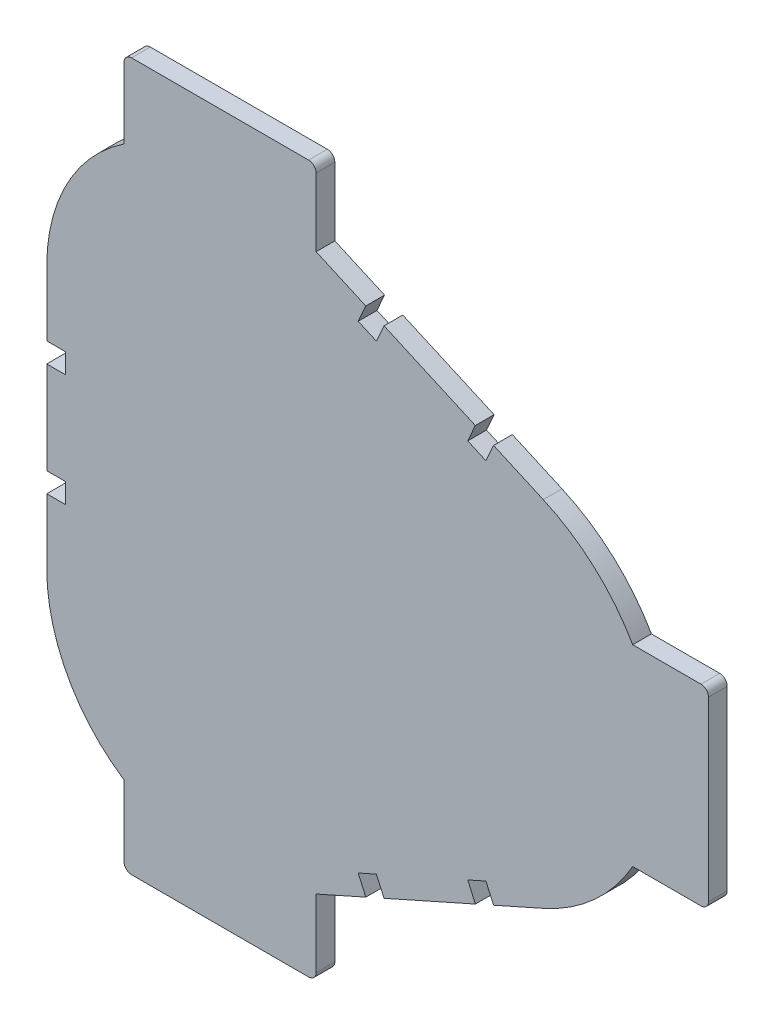
SolidWorks part; units mm, degrees
ref_plane "Front Plane" through (0, 0, 0) normal (0, 0, 1) x (1, 0, 0)
ref_plane "Top Plane" through (0, 0, 0) normal (0, 1, 0) x (1, 0, 0)
ref_plane "Right Plane" through (0, 0, 0) normal (1, 0, 0) x (0, 0, -1)
sketch "Sketch1" plane through (0, 0, -130.81) normal (0, 0, -1) x (-1, 0, 0)
  line L0 (70.5268, 62.4132) -> (70.5268, 49.4592) construction
  line L1 (70.5268, 49.4592) -> (76.8768, 49.4592) construction
  line L2 (76.8768, 49.4592) -> (76.8768, 62.4132) construction
  line L3 (76.8768, 62.4132) -> (70.5268, 62.4132) construction
  line L4 (70.5268, 24.3132) -> (70.5268, 11.3592) construction
  line L5 (70.5268, 11.3592) -> (76.8768, 11.3592) construction
  line L6 (76.8768, 11.3592) -> (76.8768, 24.3132) construction
  line L7 (76.8768, 24.3132) -> (70.5268, 24.3132) construction
  line L8 (76.8768, 52.558) -> (70.5268, 52.558) construction
  line L9 (70.5268, 52.558) -> (70.5268, 21.2144) construction
  line L10 (70.5268, 21.2144) -> (76.8768, 21.2144) construction
  line L11 (76.8768, 21.2144) -> (76.8768, 52.558) construction
  line L12 (-8.0545, -76.637) -> (-8.0545, -54.8958) construction
  line L13 (-9.5612, -52.5755) -> (-28.6575, -44.0718) construction
  line L14 (-28.6575, -44.0718) -> (-31.2406, -49.8726) construction
  line L15 (-31.2406, -49.8726) -> (-14.4045, -57.3699) construction
  line L16 (-14.4045, -57.3699) -> (-14.4045, -80.447) construction
  line L17 (-11.8645, -82.987) -> (48.143, -82.987) construction
  line L18 (50.683, -80.447) -> (50.683, -56.4617) construction
  line L19 (76.8768, -7.5638) -> (76.8768, 14.458) construction
  line L20 (76.8768, 14.458) -> (70.5268, 14.458) construction
  line L21 (70.5268, 14.458) -> (70.5268, -7.5638) construction
  line L22 (44.333, -54.3762) -> (44.333, -76.637) construction
  line L23 (44.333, -76.637) -> (-8.0545, -76.637) construction
  line L24 (-37.6604, -40.0627) -> (-40.2435, -45.8635) construction
  line L25 (-40.2435, -45.8635) -> (-28.4098, -51.1332) construction
  line L26 (-28.4098, -51.1332) -> (-25.8267, -45.3323) construction
  line L27 (-25.8267, -45.3323) -> (-37.6604, -40.0627) construction
  line L28 (-74.7857, -23.5304) -> (-77.3689, -29.3312) construction
  line L29 (-77.3689, -29.3312) -> (-65.5352, -34.6009) construction
  line L30 (-65.5352, -34.6009) -> (-62.952, -28.8001) construction
  line L31 (-62.952, -28.8001) -> (-74.7857, -23.5304) construction
  line L32 (-34.8296, -41.3233) -> (-65.7828, -27.5395) construction
  line L33 (-65.7828, -27.5395) -> (-68.366, -33.3403) construction
  line L34 (-68.366, -33.3403) -> (-37.4127, -47.1241) construction
  line L35 (-37.4127, -47.1241) -> (-34.8296, -41.3233) construction
  line L36 (-121.6907, 69.4299) -> (-144.8373, 69.4299) construction
  line L37 (-147.3773, 66.8899) -> (-147.3773, 6.8824) construction
  line L38 (-144.8373, 4.3424) -> (-121.6907, 4.3424) construction
  line L39 (-91.3743, -23.0945) -> (-74.5381, -30.5918) construction
  line L40 (-74.5381, -30.5918) -> (-71.9549, -24.791) construction
  line L41 (-71.9549, -24.791) -> (-88.7911, -17.2937) construction
  line L42 (-119.4336, 10.6924) -> (-138.4873, 10.6924) construction
  line L43 (-141.0273, 13.2324) -> (-141.0273, 60.5399) construction
  line L44 (-138.4873, 63.0799) -> (-119.4336, 63.0799) construction
  line L45 (-88.7911, 91.066) -> (-71.9549, 98.5633) construction
  line L46 (-71.9549, 98.5633) -> (-74.5381, 104.3642) construction
  line L47 (-74.5381, 104.3642) -> (-91.3743, 96.8669) construction
  line L48 (-74.7857, 97.3027) -> (-62.952, 102.5724) construction
  line L49 (-62.952, 102.5724) -> (-65.5352, 108.3732) construction
  line L50 (-65.5352, 108.3732) -> (-77.3689, 103.1036) construction
  line L51 (-77.3689, 103.1036) -> (-74.7857, 97.3027) construction
  line L52 (-68.366, 107.1127) -> (-65.7828, 101.3118) construction
  line L53 (-65.7828, 101.3118) -> (-34.8296, 115.0956) construction
  line L54 (-34.8296, 115.0956) -> (-37.4127, 120.8965) construction
  line L55 (-37.4127, 120.8965) -> (-68.366, 107.1127) construction
  line L56 (-37.6604, 113.835) -> (-25.8267, 119.1047) construction
  line L57 (-25.8267, 119.1047) -> (-28.4098, 124.9055) construction
  line L58 (-28.4098, 124.9055) -> (-40.2435, 119.6359) construction
  line L59 (-40.2435, 119.6359) -> (-37.6604, 113.835) construction
  line L60 (-28.6575, 117.8441) -> (-9.5612, 126.3479) construction
  line L61 (-8.0545, 128.6682) -> (-8.0545, 147.8693) construction
  line L62 (-5.5145, 150.4093) -> (41.793, 150.4093) construction
  line L63 (44.333, 147.8693) -> (44.333, 128.1486) construction
  line L64 (70.5268, 81.3362) -> (70.5268, 59.3144) construction
  line L65 (70.5268, 59.3144) -> (76.8768, 59.3144) construction
  line L66 (76.8768, 59.3144) -> (76.8768, 81.3362) construction
  line L67 (50.683, 130.234) -> (50.683, 154.2193) construction
  line L68 (48.143, 156.7593) -> (-11.8645, 156.7593) construction
  line L69 (-14.4045, 154.2193) -> (-14.4045, 131.1423) construction
  line L70 (-14.4045, 131.1423) -> (-31.2406, 123.6449) construction
  line L71 (-31.2406, 123.6449) -> (-28.6575, 117.8441) construction
  line L72 (70.5268, 62.4132) -> (70.5268, 49.4592)
  line L73 (70.5268, 49.4592) -> (76.8768, 49.4592)
  line L74 (76.8768, 49.4592) -> (76.8768, 62.4132)
  line L75 (76.8768, 62.4132) -> (70.5268, 62.4132)
  line L76 (70.5268, 24.3132) -> (70.5268, 11.3592)
  line L77 (70.5268, 11.3592) -> (76.8768, 11.3592)
  line L78 (76.8768, 11.3592) -> (76.8768, 24.3132)
  line L79 (76.8768, 24.3132) -> (70.5268, 24.3132)
  line L80 (76.8768, 52.558) -> (70.5268, 52.558)
  line L81 (70.5268, 52.558) -> (70.5268, 21.2144)
  line L82 (70.5268, 21.2144) -> (76.8768, 21.2144)
  line L83 (76.8768, 21.2144) -> (76.8768, 52.558)
  line L84 (-8.0545, -76.637) -> (-8.0545, -54.8958)
  line L85 (-9.5612, -52.5755) -> (-28.6575, -44.0718)
  line L86 (-28.6575, -44.0718) -> (-31.2406, -49.8726)
  line L87 (-31.2406, -49.8726) -> (-14.4045, -57.3699)
  line L88 (-14.4045, -57.3699) -> (-14.4045, -80.447)
  line L89 (-11.8645, -82.987) -> (48.143, -82.987)
  line L90 (50.683, -80.447) -> (50.683, -56.4617)
  line L91 (76.8768, -7.5638) -> (76.8768, 14.458)
  line L92 (76.8768, 14.458) -> (70.5268, 14.458)
  line L93 (70.5268, 14.458) -> (70.5268, -7.5638)
  line L94 (44.333, -54.3762) -> (44.333, -76.637)
  line L95 (44.333, -76.637) -> (-8.0545, -76.637)
  line L96 (-37.6604, -40.0627) -> (-40.2435, -45.8635)
  line L97 (-40.2435, -45.8635) -> (-28.4098, -51.1332)
  line L98 (-28.4098, -51.1332) -> (-25.8267, -45.3323)
  line L99 (-25.8267, -45.3323) -> (-37.6604, -40.0627)
  line L100 (-74.7857, -23.5304) -> (-77.3689, -29.3312)
  line L101 (-77.3689, -29.3312) -> (-65.5352, -34.6009)
  line L102 (-65.5352, -34.6009) -> (-62.952, -28.8001)
  line L103 (-62.952, -28.8001) -> (-74.7857, -23.5304)
  line L104 (-34.8296, -41.3233) -> (-65.7828, -27.5395)
  line L105 (-65.7828, -27.5395) -> (-68.366, -33.3403)
  line L106 (-68.366, -33.3403) -> (-37.4127, -47.1241)
  line L107 (-37.4127, -47.1241) -> (-34.8296, -41.3233)
  line L108 (-121.6907, 69.4299) -> (-144.8373, 69.4299)
  line L109 (-147.3773, 66.8899) -> (-147.3773, 6.8824)
  line L110 (-144.8373, 4.3424) -> (-121.6907, 4.3424)
  line L111 (-91.3743, -23.0945) -> (-74.5381, -30.5918)
  line L112 (-74.5381, -30.5918) -> (-71.9549, -24.791)
  line L113 (-71.9549, -24.791) -> (-88.7911, -17.2937)
  line L114 (-119.4336, 10.6924) -> (-138.4873, 10.6924)
  line L115 (-141.0273, 13.2324) -> (-141.0273, 60.5399)
  line L116 (-138.4873, 63.0799) -> (-119.4336, 63.0799)
  line L117 (-88.7911, 91.066) -> (-71.9549, 98.5633)
  line L118 (-71.9549, 98.5633) -> (-74.5381, 104.3642)
  line L119 (-74.5381, 104.3642) -> (-91.3743, 96.8669)
  line L120 (-74.7857, 97.3027) -> (-62.952, 102.5724)
  line L121 (-62.952, 102.5724) -> (-65.5352, 108.3732)
  line L122 (-65.5352, 108.3732) -> (-77.3689, 103.1036)
  line L123 (-77.3689, 103.1036) -> (-74.7857, 97.3027)
  line L124 (-68.366, 107.1127) -> (-65.7828, 101.3118)
  line L125 (-65.7828, 101.3118) -> (-34.8296, 115.0956)
  line L126 (-34.8296, 115.0956) -> (-37.4127, 120.8965)
  line L127 (-37.4127, 120.8965) -> (-68.366, 107.1127)
  line L128 (-37.6604, 113.835) -> (-25.8267, 119.1047)
  line L129 (-25.8267, 119.1047) -> (-28.4098, 124.9055)
  line L130 (-28.4098, 124.9055) -> (-40.2435, 119.6359)
  line L131 (-40.2435, 119.6359) -> (-37.6604, 113.835)
  line L132 (-28.6575, 117.8441) -> (-9.5612, 126.3479)
  line L133 (-8.0545, 128.6682) -> (-8.0545, 147.8693)
  line L134 (-5.5145, 150.4093) -> (41.793, 150.4093)
  line L135 (44.333, 147.8693) -> (44.333, 128.1486)
  line L136 (70.5268, 81.3362) -> (70.5268, 59.3144)
  line L137 (70.5268, 59.3144) -> (76.8768, 59.3144)
  line L138 (76.8768, 59.3144) -> (76.8768, 81.3362)
  line L139 (50.683, 130.234) -> (50.683, 154.2193)
  line L140 (48.143, 156.7593) -> (-11.8645, 156.7593)
  line L141 (-14.4045, 154.2193) -> (-14.4045, 131.1423)
  line L142 (-14.4045, 131.1423) -> (-31.2406, 123.6449)
  line L143 (-31.2406, 123.6449) -> (-28.6575, 117.8441)
  arc A0 (-8.0545, -54.8958) -> (-9.5612, -52.5755) centre (-10.5945, -54.8958) ccw construction
  arc A1 (-14.4045, -80.447) -> (-11.8645, -82.987) centre (-11.8645, -80.447) ccw construction
  arc A2 (48.143, -82.987) -> (50.683, -80.447) centre (48.143, -80.447) ccw construction
  arc A3 (50.683, -56.4617) -> (76.8768, -7.5638) centre (18.1393, -7.5638) ccw construction
  arc A4 (45.5443, -52.2115) -> (70.5268, -7.5638) centre (18.1393, -7.5638) ccw construction
  arc A5 (45.5443, -52.2115) -> (44.333, -54.3762) centre (46.873, -54.3762) ccw construction
  arc A6 (-144.8373, 69.4299) -> (-147.3773, 66.8899) centre (-144.8373, 66.8899) ccw construction
  arc A7 (-147.3773, 6.8824) -> (-144.8373, 4.3424) centre (-144.8373, 6.8824) ccw construction
  arc A8 (-121.6907, 4.3424) -> (-91.3743, -23.0945) centre (-64.6643, 36.8862) ccw construction
  arc A9 (-117.1843, 9.3325) -> (-88.7911, -17.2937) centre (-64.6643, 36.8862) ccw construction
  arc A10 (-117.1843, 9.3325) -> (-119.4336, 10.6924) centre (-119.4336, 8.1524) ccw construction
  arc A11 (-141.0273, 13.2324) -> (-138.4873, 10.6924) centre (-138.4873, 13.2324) ccw construction
  arc A12 (-138.4873, 63.0799) -> (-141.0273, 60.5399) centre (-138.4873, 60.5399) ccw construction
  arc A13 (-119.4336, 63.0799) -> (-117.1843, 64.4399) centre (-119.4336, 65.6199) ccw construction
  arc A14 (-88.7911, 91.066) -> (-117.1843, 64.4399) centre (-64.6643, 36.8862) ccw construction
  arc A15 (-91.3743, 96.8669) -> (-121.6907, 69.4299) centre (-64.6643, 36.8862) ccw construction
  arc A16 (-9.5612, 126.3479) -> (-8.0545, 128.6682) centre (-10.5945, 128.6682) ccw construction
  arc A17 (-5.5145, 150.4093) -> (-8.0545, 147.8693) centre (-5.5145, 147.8693) ccw construction
  arc A18 (44.333, 147.8693) -> (41.793, 150.4093) centre (41.793, 147.8693) ccw construction
  arc A19 (44.333, 128.1486) -> (45.5443, 125.9839) centre (46.873, 128.1486) ccw construction
  arc A20 (70.5268, 81.3362) -> (45.5443, 125.9839) centre (18.1393, 81.3362) ccw construction
  arc A21 (76.8768, 81.3362) -> (50.683, 130.234) centre (18.1393, 81.3362) ccw construction
  arc A22 (50.683, 154.2193) -> (48.143, 156.7593) centre (48.143, 154.2193) ccw construction
  arc A23 (-11.8645, 156.7593) -> (-14.4045, 154.2193) centre (-11.8645, 154.2193) ccw construction
  arc A24 (-8.0545, -54.8958) -> (-9.5612, -52.5755) centre (-10.5945, -54.8958) ccw
  arc A25 (-14.4045, -80.447) -> (-11.8645, -82.987) centre (-11.8645, -80.447) ccw
  arc A26 (48.143, -82.987) -> (50.683, -80.447) centre (48.143, -80.447) ccw
  arc A27 (50.683, -56.4617) -> (76.8768, -7.5638) centre (18.1393, -7.5638) ccw
  arc A28 (45.5443, -52.2115) -> (70.5268, -7.5638) centre (18.1393, -7.5638) ccw
  arc A29 (45.5443, -52.2115) -> (44.333, -54.3762) centre (46.873, -54.3762) ccw
  arc A30 (-144.8373, 69.4299) -> (-147.3773, 66.8899) centre (-144.8373, 66.8899) ccw
  arc A31 (-147.3773, 6.8824) -> (-144.8373, 4.3424) centre (-144.8373, 6.8824) ccw
  arc A32 (-121.6907, 4.3424) -> (-91.3743, -23.0945) centre (-64.6643, 36.8862) ccw
  arc A33 (-117.1843, 9.3325) -> (-88.7911, -17.2937) centre (-64.6643, 36.8862) ccw
  arc A34 (-117.1843, 9.3325) -> (-119.4336, 10.6924) centre (-119.4336, 8.1524) ccw
  arc A35 (-141.0273, 13.2324) -> (-138.4873, 10.6924) centre (-138.4873, 13.2324) ccw
  arc A36 (-138.4873, 63.0799) -> (-141.0273, 60.5399) centre (-138.4873, 60.5399) ccw
  arc A37 (-119.4336, 63.0799) -> (-117.1843, 64.4399) centre (-119.4336, 65.6199) ccw
  arc A38 (-88.7911, 91.066) -> (-117.1843, 64.4399) centre (-64.6643, 36.8862) ccw
  arc A39 (-91.3743, 96.8669) -> (-121.6907, 69.4299) centre (-64.6643, 36.8862) ccw
  arc A40 (-9.5612, 126.3479) -> (-8.0545, 128.6682) centre (-10.5945, 128.6682) ccw
  arc A41 (-5.5145, 150.4093) -> (-8.0545, 147.8693) centre (-5.5145, 147.8693) ccw
  arc A42 (44.333, 147.8693) -> (41.793, 150.4093) centre (41.793, 147.8693) ccw
  arc A43 (44.333, 128.1486) -> (45.5443, 125.9839) centre (46.873, 128.1486) ccw
  arc A44 (70.5268, 81.3362) -> (45.5443, 125.9839) centre (18.1393, 81.3362) ccw
  arc A45 (76.8768, 81.3362) -> (50.683, 130.234) centre (18.1393, 81.3362) ccw
  arc A46 (50.683, 154.2193) -> (48.143, 156.7593) centre (48.143, 154.2193) ccw
  arc A47 (-11.8645, 156.7593) -> (-14.4045, 154.2193) centre (-11.8645, 154.2193) ccw
  line M24 (-121.6907, 69.4299) -> (-144.8373, 69.4299)
  arc M25 (-144.8373, 69.4299) -> (-147.3773, 66.8899) centre (-144.8373, 66.8899) ccw
  line M26 (-147.3773, 66.8899) -> (-147.3773, 6.8824)
  arc M27 (-147.3773, 6.8824) -> (-144.8373, 4.3424) centre (-144.8373, 6.8824) ccw
  line M28 (-144.8373, 4.3424) -> (-121.6907, 4.3424)
  arc M29 (-121.6907, 4.3424) -> (-91.3743, -23.0945) centre (-64.6643, 36.8862) ccw
  line M30 (-91.3743, -23.0945) -> (-74.5381, -30.5918)
  line M31 (-74.5381, -30.5918) -> (-71.9549, -24.791)
  line M32 (-71.9549, -24.791) -> (-88.7911, -17.2937)
  arc M33 (-88.7911, -17.2937) -> (-117.1843, 9.3325) centre (-64.6643, 36.8862) cw
  arc M34 (-117.1843, 9.3325) -> (-119.4336, 10.6924) centre (-119.4336, 8.1524) ccw
  line M35 (-119.4336, 10.6924) -> (-138.4873, 10.6924)
  arc M36 (-138.4873, 10.6924) -> (-141.0273, 13.2324) centre (-138.4873, 13.2324) cw
  line M37 (-141.0273, 13.2324) -> (-141.0273, 60.5399)
  arc M38 (-141.0273, 60.5399) -> (-138.4873, 63.0799) centre (-138.4873, 60.5399) cw
  line M39 (-138.4873, 63.0799) -> (-119.4336, 63.0799)
  arc M40 (-119.4336, 63.0799) -> (-117.1843, 64.4399) centre (-119.4336, 65.6199) ccw
  arc M41 (-117.1843, 64.4399) -> (-88.7911, 91.066) centre (-64.6643, 36.8862) cw
  line M42 (-88.7911, 91.066) -> (-71.9549, 98.5633)
  line M43 (-71.9549, 98.5633) -> (-74.5381, 104.3642)
  line M44 (-74.5381, 104.3642) -> (-91.3743, 96.8669)
  arc M45 (-91.3743, 96.8669) -> (-121.6907, 69.4299) centre (-64.6643, 36.8862) ccw
extrude "Boss-Extrude1" add sketch "Sketch1" along normal blind 6.35 contours L136 A44 A43 L135 A42 L134 A41 L133 A40 L132 L128 L125 L120 L117 L103 L104 L99 L85 A24 L84 L95 L94 A29 A28 L93 L76 L81 L72 M42 M41 M40 M39 M38 M37 M36 M35 M34 M33 M32 | L72 L137 L74 L75 | L140 A47 L141 L142 L129 L132 A40 L133 A41 L134 A42 L135 A43 A44 L136 L75 L138 A45 L139 A46 | L74 L80 L72 L73 | L79 L83 L73 L81 | L76 L82 L78 L79 | L78 L92 L76 L77 | A28 A29 L94 L95 L84 A24 L85 L98 L87 L88 A25 L89 A26 L90 A27 L91 L77 L93 | L87 L98 L85 L86 | L97 L107 L99 L96 | L102 L106 L96 L104 | L103 L105 L101 L102 | L123 L119 L100 M45 M24 M25 M26 M27 M28 M29 M30 M32 M33 M34 M35 M36 M37 M38 M39 M40 M41 M42 | L100 M32 M30 M31 | L131 L127 L121 L125 | L127 L131 L125 L126 | L130 L143 L128 L129 | L122 L124 L120 L121 | L123 L117 M44 M43 region at (-73.7018, 60.8638, -130.81) region at (-71.9405, 71.8747, -130.81) region at (15.8839, 36.8762, -130.81) region at (-73.7018, 51.0086, -130.81) region at (-73.7018, 36.8862, -130.81) region at (-73.7018, 22.7638, -130.81) region at (-73.7018, 12.9086, -130.81) region at (-73.7018, 9.9454, -130.81) region at (28.5336, 121.3748, -130.81) region at (37.5365, 117.3657, -130.81) region at (51.5978, 111.1041, -130.81) region at (65.659, 104.8425, -130.81) region at (28.5336, -47.6025, -130.81) region at (74.6619, 100.8335, -130.81) region at (77.457, 99.5888, -130.81) region at (37.5365, -43.5934, -130.81) region at (51.5978, -37.3318, -130.81) region at (65.659, -31.0702, -130.81) region at (74.6619, -27.0611, -130.81)
